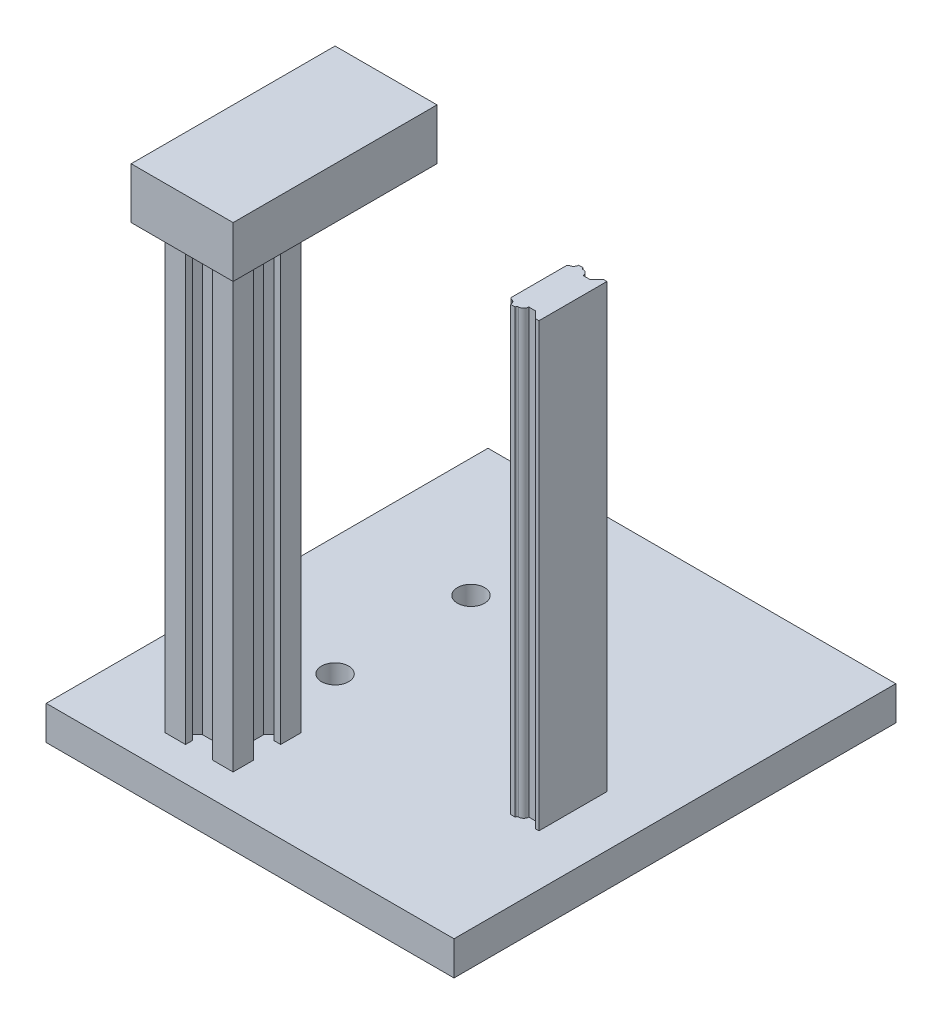
SolidWorks part; units mm, degrees
ref_plane "Front Plane" through (0, 0, 0) normal (0, 0, 1) x (1, 0, 0)
ref_plane "Top Plane" through (0, 0, 0) normal (0, 1, 0) x (1, 0, 0)
ref_plane "Right Plane" through (0, 0, 0) normal (1, 0, 0) x (0, 0, -1)
sketch "Sketch1" plane through (0, 0, 0) normal (0, 1, 0) x (1, 0, 0)
  line L1 (-60, 65) -> (60, 65)
  line L2 (-60, 65) -> (-60, -65)
  line L3 (-60, -65) -> (60, -65)
  line L4 (60, 65) -> (60, -65)
  line L5 (-60, 65) -> (60, -65) construction
  line L6 (-60, -65) -> (60, 65) construction
  point P0 (0, 0)
  dimension "D1" = 120
  dimension "D2" = 130
extrude "BaseMount" add sketch "Sketch1" along normal blind 10
ref_plane "mirroring plane" through (0, 0, 0) normal (1, 0, 0) x (0, 0, -1)
sketch "Sketch4" plane through (0, 10, 0) normal (0, 1, 0) x (1, 0, 0)
  line L0 (60, -65) -> (60, 65) construction
  line L1 (45, -15) -> (35, -15)
  line L2 (45, -15) -> (45, -5)
  line L3 (45, -5) -> (35, -5)
  line L4 (35, -15) -> (35, -5)
  line L5 (60, 65) -> (-60, 65) construction
  dimension "D1" = 10
  dimension "D2" = 10
  dimension "D3" = 15
  dimension "D4" = 70
extrude "Boss-Extrude3" add sketch "Sketch4" along normal blind 130 separate body
sketch "Sketch5" plane through (0, 140, 0) normal (0, 1, 0) x (1, 0, 0)
  line L0 (44, -5) -> (42, -7)
  line L1 (45, -5) -> (35, -5) construction
  line L2 (42, -7) -> (40, -7)
  line L3 (38, -5) -> (44, -5)
  line L4 (35, -6.9757) -> (35, -5)
  line L5 (35, -5) -> (35, -15) construction
  line L6 (35, -5) -> (36.6893, -5)
  line L7 (45, -15) -> (45, -5) construction
  line L8 (45, 3.6875) -> (44.5, 4.2491)
  line L9 (44.5, 4.2491) -> (44.5, 5.2423)
  line L10 (44.5, 5.2423) -> (45, 5.6875)
  line L11 (45, 5.6875) -> (45, 3.6875)
  arc A1 (38, -5) -> (38.5, -5.5) centre (38.5, -5) ccw
  arc A2 (38.5, -5.5) -> (40, -7) centre (38.5, -7) cw
  arc A3 (36.6893, -5) -> (35.4223, -6.4818) centre (35.1893, -5) cw
  arc A4 (35.4223, -6.4818) -> (35, -6.9757) centre (35.5, -6.9757) ccw
  dimension "D1" = 1.5
  dimension "D4" = 135
  dimension "D6" = 0.5
  dimension "D7" = 1.5
  dimension "D8" = 0.5
  dimension "D2" = 2
  dimension "D3" = 2
  dimension "D5" = 1
  dimension "D9" = 2
  dimension "D10" = 0.5
extrude "Cut-Extrude2" cut sketch "Sketch5" against normal blind 130
mirror "Mirror9" about plane through (45, 140, 15) normal (0, 0, -1) of "Cut-Extrude2", "Boss-Extrude3"
ref_axis "lengthRe" through (45, 10, 5) along (0, 0, 1)
ref_point "centerPointRef"
sketch "Sketch6" plane through (0, 10, 0) normal (0, 1, 0) x (1, 0, 0)
  line L8 (45, -5) -> (45, -25) construction
  circle A0 centre (-25, -15) radius 4
  circle A1 centre (-25, 25) radius 4
  point P0 (-25, -15)
  dimension "D3" = 8
  dimension "D4" = 8
  dimension "D1" = 70
  dimension "D2" = 40
extrude "Cut-Extrude3" cut sketch "Sketch6" against normal blind 10
sketch "Sketch7" plane through (0, 10, 0) normal (0, 1, 0) x (1, 0, 0)
  line L5 (45, -25) -> (45, -5) construction
  line L6 (-15, -35) -> (-35, -35)
  line L10 (-15, -35) -> (-15, -55)
  line L11 (-15, -55) -> (-35, -55)
  line L12 (-35, -35) -> (-35, -55)
  line L13 (-15, -35) -> (-35, -55) construction
  line L14 (-15, -55) -> (-35, -35) construction
  circle A1 centre (-25, -15) radius 4 construction
  point P0 (-25, -45)
  dimension "D3" = 30
  dimension "D1" = 20
  dimension "D2" = 20
  dimension "D4" = 70
extrude "frontBar" add sketch "Sketch7" along normal blind 130
sketch "Sketch8" plane through (0, 140, 0) normal (0, 1, 0) x (1, 0, 0)
  line L34 (-29, -41) -> (-29, -49)
  line L35 (-29, -49) -> (-21, -49)
  line L36 (-21, -49) -> (-21, -41)
  line L37 (-21, -41) -> (-29, -41)
  line L38 (-29, -41) -> (-29, -49)
  line L39 (-29, -49) -> (-21, -49)
  line L40 (-21, -49) -> (-21, -41)
  line L41 (-21, -41) -> (-29, -41)
  dimension "D1" = 6
extrude "centercut" cut sketch "Sketch8" against normal blind 130
ref_point "circularMirrorP1"
ref_point "cicularMirrorP2"
ref_axis "cicularMirrorAxis" through (-25, 10, 45) along (0, 1, 0)
sketch "Sketch10" plane through (0, 140, 0) normal (0, 1, 0) x (1, 0, 0)
  line L0 (-32, -53) -> (-29, -53)
  line L1 (-29, -53) -> (-29, -55)
  line L3 (-29, -55) -> (-21, -55)
  line L4 (-21, -55) -> (-21, -53)
  line L5 (-21, -53) -> (-18, -53)
  line L6 (-18, -53) -> (-21, -50)
  line L7 (-21, -50) -> (-29, -50)
  line L8 (-29, -50) -> (-32, -53)
  line L9 (-35, -55) -> (-15, -55) construction
  line L10 (-29, -49) -> (-21, -49) construction
  point P12 (0, 0)
  point P14 (0, 0)
  point P16 (0, 0)
  point P17 (0, 0)
  point P18 (0, 0)
  point P19 (-22.1728, -55)
  point P22 (-25, -55)
  point P23 (-25, -55)
  point P24 (-25, -50)
  dimension "D1" = 2
  dimension "D2" = 8
  dimension "D3" = 1
  dimension "D4" = 45
  dimension "D5" = 45
extrude "siteCutBasic" cut sketch "Sketch10" against normal blind 130
pattern_circular "siteCutMirror" count 4 over 360 about axis through (-25, 10, 45) along (0, 1, 0) of "siteCutBasic"
ref_plane "centerScrewHolderRef" through (0, 140, 0) normal (0, 1, 0) x (1, 0, 0)
sketch "Sketch11" plane through (0, 140, 0) normal (0, 1, 0) x (1, 0, 0)
  line L0 (-21, -55) -> (-15, -55) construction
  line L1 (-10, -60) -> (-40, -60)
  line L2 (-10, -60) -> (-10, 0)
  line L3 (-10, 0) -> (-40, 0)
  line L4 (-40, -60) -> (-40, 0)
  line L5 (-35, -35) -> (-35, -41) construction
  dimension "D1" = 30
  dimension "D2" = 60
  dimension "D3" = 5
  dimension "D4" = 5
extrude "upperBody" add sketch "Sketch11" along normal blind 15
ref_axis "centerAxis" through (-25, 0, 15) along (0, 1, 0)
sketch "Sketch13" plane through (0, 140, 0) normal (0, -1, 0) x (1, 0, 0)
  circle A0 centre (-25, 15) radius 4
  dimension "D1" = 8
extrude "Cut-Extrude6" cut sketch "Sketch13" against normal blind 10
